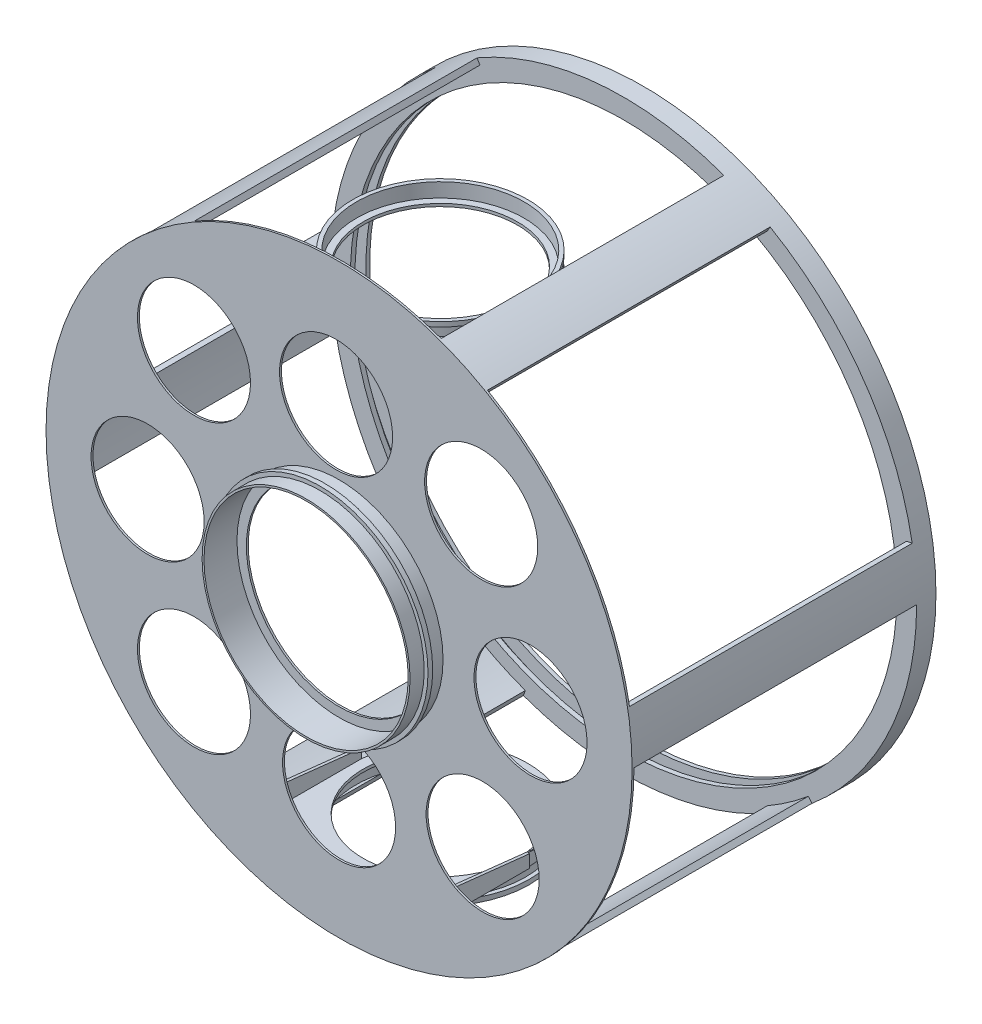
SolidWorks part; units mm, degrees
ref_plane "Front Plane" through (0, 0, 0) normal (0, 0, 1) x (1, 0, 0)
ref_plane "Top Plane" through (0, 0, 0) normal (0, 1, 0) x (1, 0, 0)
ref_plane "Right Plane" through (0, 0, 0) normal (1, 0, 0) x (0, 0, -1)
sketch "Sketch1" plane through (0, 0, 0) normal (0, 0, 1) x (1, 0, 0)
  circle A0 centre (0, 0) radius 290.1
  circle A1 centre (0, 0) radius 311
extrude "Extrude1" add sketch "Sketch1" along normal blind 4
sketch "Sketch3" plane through (0, 0, 4) normal (0, 0, 1) x (1, 0, 0)
  circle A0 centre (0, 0) radius 311
  circle A1 centre (0, 0) radius 305
extrude "Extrude2" add sketch "Sketch3" along normal blind 11.5
sketch "Sketch4" plane through (0, 0, 15.5) normal (0, 0, 1) x (1, 0, 0)
  circle A0 centre (0, 0) radius 311
  circle A1 centre (0, 0) radius 290.1
extrude "Extrude3" add sketch "Sketch4" along normal blind 5
sketch "Sketch5" plane through (0, 0, 20.5) normal (0, 0, 1) x (1, 0, 0)
  line L0 (0, 0) -> (190.5, 0) construction
  line L1 (0, 0) -> (106.0987, 183.7684) construction
  line L2 (0, 0) -> (-108.3258, 187.6258) construction
  line L3 (0, 0) -> (-211.1375, 0) construction
  line L4 (0, 0) -> (-109.7214, -190.043) construction
  line L5 (0, 0) -> (117.9514, -204.2977) construction
  line L6 (0, 0) -> (268.0733, 47.2686) construction
  line L7 (0, 0) -> (77.8476, 213.8846) construction
  line L8 (0, 0) -> (-153.0298, 182.3738) construction
  line L9 (0, 0) -> (-259.4461, -45.7473) construction
  line L10 (0, 0) -> (-74.3455, -204.2625) construction
  line L11 (0, 0) -> (154.9569, -184.6704) construction
  line L12 (300.3664, 52.9627) -> (306.2752, 54.0046)
  line L13 (305, 0) -> (311, 0)
  line L14 (152.5, 264.1377) -> (155.5, 269.3339)
  line L15 (104.3161, 286.6062) -> (106.3683, 292.2444)
  line L16 (-152.5, 264.1377) -> (-155.5, 269.3339)
  line L17 (-196.0502, 233.6436) -> (-199.9069, 238.2398)
  line L18 (-305, 0) -> (-311, 0)
  line L19 (-300.3664, -52.9627) -> (-306.2752, -54.0046)
  line L20 (-152.5, -264.1377) -> (-155.5, -269.3339)
  line L21 (-104.3161, -286.6062) -> (-106.3683, -292.2444)
  line L22 (152.5, -264.1377) -> (155.5, -269.3339)
  line L23 (196.0502, -233.6436) -> (199.9069, -238.2398)
  circle A0 centre (0, 0) radius 311 construction
  circle A1 centre (0, 0) radius 305 construction
  arc A2 (300.3664, 52.9627) -> (305, 0) centre (0, 0) cw
  arc A3 (104.3161, 286.6062) -> (152.5, 264.1377) centre (0, 0) cw
  arc A4 (155.5, 269.3339) -> (106.3683, 292.2444) centre (0, 0) ccw
  arc A6 (-152.5, 264.1377) -> (-196.0502, 233.6436) centre (0, 0) ccw
  arc A7 (-155.5, 269.3339) -> (-199.9069, 238.2398) centre (0, 0) ccw
  arc A8 (-305, 0) -> (-300.3664, -52.9627) centre (0, 0) ccw
  arc A9 (-311, 0) -> (-306.2752, -54.0046) centre (0, 0) ccw
  arc A10 (-152.5, -264.1377) -> (-104.3161, -286.6062) centre (0, 0) ccw
  arc A11 (-155.5, -269.3339) -> (-106.3683, -292.2444) centre (0, 0) ccw
  arc A12 (152.5, -264.1377) -> (196.0502, -233.6436) centre (0, 0) ccw
  arc A13 (155.5, -269.3339) -> (199.9069, -238.2398) centre (0, 0) ccw
  arc A14 (311, 0) -> (306.2752, 54.0046) centre (0, 0) ccw
extrude "Extrude4" add sketch "Sketch5" along normal blind 300
sketch "Sketch6" plane through (0, 0, 320.5) normal (0, 0, 1) x (1, 0, 0)
  circle A0 centre (0, 0) radius 311
extrude "Extrude5" add sketch "Sketch6" along normal blind 2
sketch "Sketch7" plane through (0, 0, 322.5) normal (0, 0, 1) x (1, 0, 0)
  circle A0 centre (0, 0) radius 110.37
  circle A1 centre (0, 0) radius 108.37
extrude "Extrude6" add sketch "Sketch7" along normal blind 15
sketch "Sketch8" plane through (0, 0, 337.5) normal (0, 0, 1) x (1, 0, 0)
  circle A0 centre (0, 0) radius 108.37
  circle A1 centre (0, 0) radius 114.4
extrude "Extrude7" add sketch "Sketch8" along normal blind 5
sketch "Sketch9" plane through (0, 0, 342.5) normal (0, 0, 1) x (1, 0, 0)
  circle A0 centre (0, 0) radius 108.37
  circle A1 centre (0, 0) radius 110.37
extrude "Extrude8" add sketch "Sketch9" along normal blind 15
sketch "Sketch10" plane through (0, 0, 320.5) normal (0, 0, -1) x (-1, 0, 0)
  line L0 (0, 0) -> (0, 334.2218) construction
  line L1 (0, 0) -> (0, -343.8771) construction
  line L2 (0, 250) -> (502.8181, 250) construction
  line L3 (0, 250) -> (-514.35, 250) construction
  line L4 (0, -250) -> (542.182, -250) construction
  line L5 (0, -250) -> (-551.8374, -250) construction
  line L6 (0, 253) -> (404.821, 253) construction
  line L7 (0, 253) -> (-322.9253, 253) construction
  line L8 (0, -253) -> (377.1337, -253) construction
  line L9 (0, -253) -> (-458.931, -253) construction
  line L10 (94.96, 250) -> (94.96, 228)
  line L11 (94.96, 250) -> (94.96, 253)
  line L12 (94.96, 253) -> (0, 253)
  line L13 (0, 253) -> (-94.96, 253)
  line L14 (-94.96, 253) -> (-94.96, 250)
  line L15 (94.96, -250) -> (94.96, -228)
  line L16 (94.96, -250) -> (94.96, -253)
  line L17 (94.96, -253) -> (-94.96, -253)
  line L18 (-94.96, -253) -> (-94.96, -250)
  line L19 (94.96, 253) -> (94.96, 166.3555) construction
  line L20 (-94.96, 253) -> (-94.96, 171.8799) construction
  line L21 (94.96, -253) -> (94.96, -186.8569) construction
  line L22 (-94.96, -253) -> (-94.96, -186.8569) construction
  line L23 (94.96, -228) -> (-94.96, -228) construction
  line L24 (94.96, 228) -> (-94.96, 228) construction
  line L25 (94.96, 228) -> (91.96, 228)
  line L26 (91.96, 228) -> (91.96, 250)
  line L27 (91.96, 250) -> (-91.96, 250)
  line L28 (-91.96, 250) -> (-91.96, 228)
  line L29 (-91.96, 228) -> (-94.96, 228)
  line L30 (-94.96, 228) -> (-94.96, 250)
  line L31 (94.96, -228) -> (91.96, -228)
  line L32 (91.96, -228) -> (91.96, -250)
  line L33 (91.96, -250) -> (-91.96, -250)
  line L34 (-91.96, -250) -> (-91.96, -228)
  line L35 (-91.96, -228) -> (-94.96, -228)
  line L36 (-94.96, -228) -> (-94.96, -250)
  point P3 (0, 250)
  point P5 (0, -250)
  point P11 (0, 253)
  point P13 (0, -253)
  point P19 (94.96, 250)
  point P21 (-94.96, 250)
  point P22 (94.96, -250)
  point P23 (-94.96, -250)
  point P30 (94.96, 228)
  point P35 (-94.96, 228)
  point P36 (94.96, -228)
  point P38 (-94.96, -228)
  point P42 (91.96, -228)
  point P45 (-91.96, 228)
  point P46 (91.96, 228)
  point P47 (-91.96, -228)
  dimension "D1" = 250
  dimension "FROM_C" = 250
  dimension "D2" = 3
  dimension "D3" = 3
  dimension "D4" = 94.96
  dimension "RAD" = 94.96
  dimension "D5" = 94.96
  dimension "D6" = 94.96
  dimension "D7" = 25
  dimension "STRONG" = 25
  dimension "D8" = 25
  dimension "D9" = 25
  dimension "D10" = 3
  dimension "D11" = 3
  dimension "D12" = 3
extrude "Extrude9" add sketch "Sketch10" along normal blind 200
sketch "Sketch11" plane through (0, 253, 0) normal (0, 1, 0) x (1, 0, 0)
  line L0 (-94.96, -120.5) -> (94.96, -120.5) construction
  line L1 (0.3935, -99.9484) -> (0.3935, -349.6766) construction
  circle A0 centre (0.3935, -215.46) radius 90.96
  circle A1 centre (0.3935, -215.46) radius 88.96
  point P0 (0, -120.5)
  point P5 (0.3935, -215.46)
  dimension "D1" = 94.96
extrude "Extrude10" add sketch "Sketch11" along normal blind 10
sketch "Sketch13" plane through (0, 263, 0) normal (0, 1, 0) x (1, 0, 0)
  circle A0 centre (0.3935, -215.46) radius 88.96
  circle A1 centre (0.3935, -215.46) radius 92.96
extrude "Extrude11" add sketch "Sketch13" along normal blind 5
sketch "Sketch14" plane through (0, -253, 0) normal (0, -1, 0) x (1, 0, 0)
  line L0 (94.96, 120.5) -> (-94.96, 120.5) construction
  line L1 (0, 120.5) -> (0, 386.5869) construction
  circle A0 centre (0, 215.46) radius 88.96
  circle A1 centre (0, 215.46) radius 90.96
  point P0 (0, 120.5)
  point P5 (0, 215.46)
  dimension "D1" = 94.96
extrude "Extrude12" add sketch "Sketch14" along normal blind 10
sketch "Sketch15" plane through (0, -263, 0) normal (0, -1, 0) x (1, 0, 0)
  circle A0 centre (0, 215.46) radius 88.96
  circle A1 centre (0, 215.46) radius 94.96
extrude "Extrude13" add sketch "Sketch15" along normal blind 5
sketch "Sketch16" plane through (91.96, 0, 0) normal (-1, 0, 0) x (0, 0, 1)
  line L0 (120.5, 228) -> (320.5, 228) construction
  line L1 (120.5, 228) -> (320.5, 228)
  line L2 (320.5, 228) -> (120.5, 250)
  line L3 (120.5, 228) -> (120.5, 250)
  point P0 (220.5, 228)
  point P1 (120.5, 250)
  point P4 (120.5, 228)
  point P9 (320.5, 228)
extrude "Extrude14" cut sketch "Sketch16" against normal up to surface and the other way up to surface up to face at (94.96, 240.5, 220.5) other way up to face at (-94.96, 240.5, 220.5)
sketch "Sketch17" plane through (-91.96, 0, 0) normal (1, 0, 0) x (0, 0, -1)
  line L0 (-120.5, -228) -> (-320.5, -228) construction
  line L1 (-320.5, -228) -> (-120.5, -228)
  line L2 (-120.5, -228) -> (-120.5, -250)
  line L3 (-120.5, -250) -> (-320.5, -228)
  point P0 (-120.5, -250)
  point P1 (-220.5, -228)
  point P3 (-120.5, -228)
  point P6 (-320.5, -228)
extrude "Extrude15" cut sketch "Sketch17" against normal up to surface and the other way up to surface up to face at (-94.96, -240.5, 220.5) other way up to face at (94.96, -240.5, 220.5)
sketch "Sketch18" plane through (0, 253, 0) normal (0, 1, 0) x (1, 0, 0)
  line L1 (93.1735, -215.46) -> (94.96, -215.46)
  line L2 (94.96, -120.5) -> (94.96, -320.5) construction
  line L3 (94.96, -215.46) -> (94.96, -120.5)
  line L4 (94.96, -120.5) -> (-94.96, -120.5)
  line L5 (-94.96, -120.5) -> (-94.96, -215.46)
  line L6 (-94.96, -120.5) -> (-94.96, -320.5) construction
  line L7 (-94.96, -215.46) -> (-92.3865, -215.46)
  circle A0 centre (69.85, -304.8) radius 11.1125
  circle A1 centre (-69.85, -304.8) radius 11.1125
  circle A2 centre (0.3935, -215.46) radius 92.78 construction
  arc A3 (93.1735, -215.46) -> (-92.3865, -215.46) centre (0.3935, -215.46) ccw
  circle A4 centre (0.3935, -215.46) radius 82
  point P9 (94.96, -120.5)
  point P12 (-94.96, -120.5)
extrude "Extrude16" cut sketch "Sketch18" against normal blind 25
sketch "Sketch19" plane through (0, -253, 0) normal (0, -1, 0) x (1, 0, 0)
  line L1 (93.1735, 215.46) -> (94.96, 215.46)
  line L2 (94.96, 215.46) -> (94.96, 120.5)
  line L3 (94.96, 120.5) -> (-94.96, 120.5)
  line L4 (-94.96, 120.5) -> (-94.96, 215.46)
  line L5 (-94.96, 215.46) -> (-92.3865, 215.46)
  circle A0 centre (69.85, 304.8) radius 11.1125
  circle A1 centre (-69.85, 304.8) radius 11.1125
  circle A2 centre (0.3935, 215.46) radius 92.78 construction
  arc A3 (93.1735, 215.46) -> (-92.3865, 215.46) centre (0.3935, 215.46) cw
  circle A4 centre (0, 215.46) radius 94.96 construction
  circle A5 centre (0.3935, 215.46) radius 82
  point P0 (69.85, 304.8)
  point P1 (-69.85, 304.8)
  point P8 (0.3935, 215.46)
extrude "Extrude18" cut sketch "Sketch19" against normal blind 25
sketch "Sketch20" plane through (0, 0, 322.5) normal (0, 0, 1) x (1, 0, 0)
  circle A0 centre (0, 0) radius 98.425
  circle A1 centre (203.2, 0) radius 60
  circle A2 centre (150.8125, 153.9875) radius 60
  circle A3 centre (-3.175, 177.8) radius 60
  circle A4 centre (-153.9875, 152.4) radius 60
  circle A5 centre (-203.2, 0) radius 60
  circle A6 centre (-153.9875, -152.4) radius 60
  circle A7 centre (0, -179.3875) radius 60
  circle A8 centre (152.4, -150.8125) radius 60
  point P3 (-153.9875, 152.4)
  point P4 (150.8125, 153.9875)
  point P5 (152.4, -150.8125)
  point P6 (-153.9875, -152.4)
  point P7 (203.2, 0)
  point P8 (-203.2, 0)
  point P9 (-3.175, 177.8)
  point P10 (0, -179.3875)
extrude "Extrude19" cut sketch "Sketch20" against normal up to surface (2 mm away) up to face at (0, 239.75, 320.5)
equation "\"D1@Sketch10\" = \"FROM_C\""
equation "\"D4@Sketch10\" = \"RAD\""
equation "\"D5@Sketch10\" = \"RAD\""
equation "\"D6@Sketch10\" = \"RAD\""
equation "\"D7@Sketch10\" = \"STRONG\""
equation "\"D8@Sketch10\" = \"STRONG\""
equation "\"D9@Sketch10\" = \"STRONG\""
